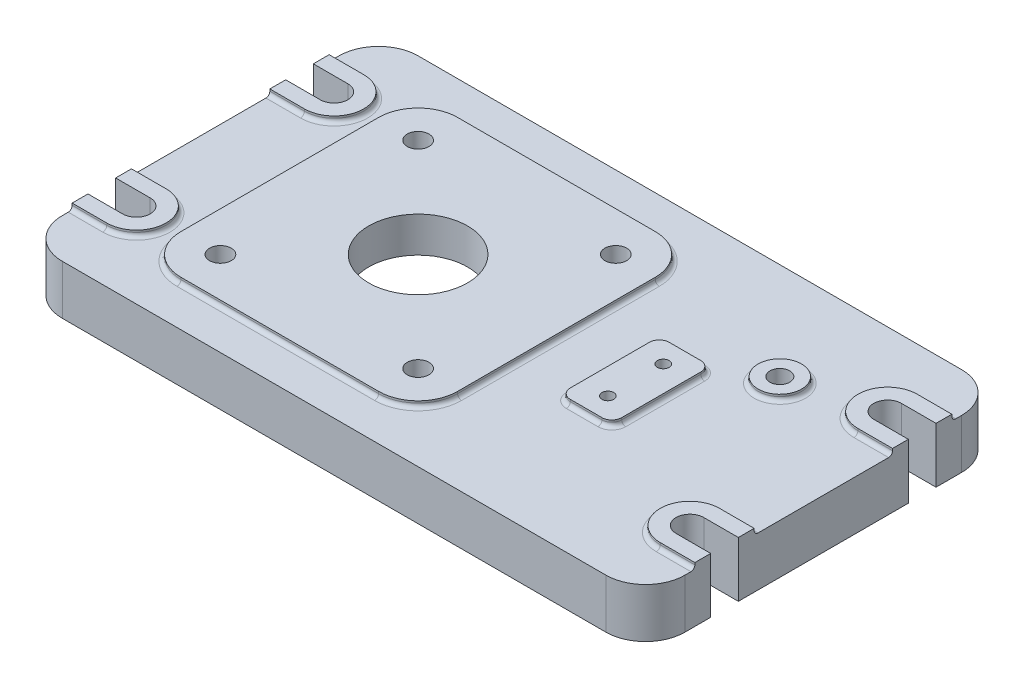
SolidWorks part; units mm, degrees
material "Gray Cast Iron"
ref_plane "Front Plane" through (0, 0, 0) normal (0, 0, 1) x (1, 0, 0)
ref_plane "Top Plane" through (0, 0, 0) normal (0, 1, 0) x (1, 0, 0)
ref_plane "Right Plane" through (0, 0, 0) normal (1, 0, 0) x (0, 0, -1)
sketch "Sketch1" plane through (0, 0, 0) normal (0, 1, 0) x (1, 0, 0)
  line L0 (-157.5, 65) -> (-140, 65)
  line L1 (-137.5, 90) -> (137.5, 90)
  line L2 (-157.5, 70) -> (-157.5, 57)
  line L3 (-137.5, -90) -> (137.5, -90)
  line L4 (157.5, 70) -> (157.5, 57)
  line L5 (-140, 35) -> (-157.5, 35)
  line L6 (-157.5, 57) -> (-140, 57)
  line L7 (-140, 43) -> (-157.5, 43)
  line L8 (-258.92, 0) -> (211.701, 0) construction
  line L9 (0, 169.4459) -> (0, -119.6728) construction
  line L10 (-140, -43) -> (-157.5, -43)
  line L11 (-157.5, -57) -> (-140, -57)
  line L12 (-140, -35) -> (-157.5, -35)
  line L13 (-157.5, -65) -> (-140, -65)
  line L14 (258.92, 0) -> (-211.701, 0) construction
  line L15 (157.5, -65) -> (140, -65)
  line L16 (140, -35) -> (157.5, -35)
  line L17 (157.5, -57) -> (140, -57)
  line L18 (140, -43) -> (157.5, -43)
  line L19 (140, 43) -> (157.5, 43)
  line L20 (157.5, 57) -> (140, 57)
  line L21 (140, 35) -> (157.5, 35)
  line L22 (157.5, 65) -> (140, 65)
  line L23 (-157.5, 43) -> (-157.5, -43)
  line L24 (-157.5, -57) -> (-157.5, -70)
  line L25 (157.5, 43) -> (157.5, -43)
  line L26 (157.5, -57) -> (157.5, -70)
  line L27 (-47.5, 101.8482) -> (-47.5, -105.2929) construction
  line L28 (-97.5, 70) -> (2.5, 70)
  line L29 (-117.5, 50) -> (-117.5, -50)
  line L30 (-97.5, -70) -> (2.5, -70)
  line L31 (22.5, 50) -> (22.5, -50)
  line L33 (54.5, 25) -> (70.5, 25)
  line L34 (49.5, 20) -> (49.5, -20)
  line L35 (54.5, -25) -> (70.5, -25)
  line L36 (75.5, 20) -> (75.5, -20)
  arc A0 (137.5, 90) -> (157.5, 70) centre (137.5, 70) cw
  arc A1 (-157.5, -70) -> (-137.5, -90) centre (-137.5, -70) ccw
  arc A2 (137.5, -90) -> (157.5, -70) centre (137.5, -70) ccw
  arc A3 (-137.5, 90) -> (-157.5, 70) centre (-137.5, 70) ccw
  arc A4 (-140, 65) -> (-140, 35) centre (-140, 50) cw
  arc A5 (-140, 57) -> (-140, 43) centre (-140, 50) cw
  arc A6 (-140, -57) -> (-140, -43) centre (-140, -50) ccw
  arc A7 (-140, -65) -> (-140, -35) centre (-140, -50) ccw
  arc A8 (140, -65) -> (140, -35) centre (140, -50) cw
  arc A9 (140, -57) -> (140, -43) centre (140, -50) cw
  arc A10 (140, 57) -> (140, 43) centre (140, 50) ccw
  arc A11 (140, 65) -> (140, 35) centre (140, 50) ccw
  arc A12 (2.5, 70) -> (22.5, 50) centre (2.5, 50) cw
  arc A13 (-117.5, -50) -> (-97.5, -70) centre (-97.5, -50) ccw
  arc A14 (2.5, -70) -> (22.5, -50) centre (2.5, -50) ccw
  arc A15 (-97.5, 70) -> (-117.5, 50) centre (-97.5, 50) ccw
  circle A16 centre (-47.5, 0) radius 25
  circle A17 centre (-97.5, 50) radius 5.5
  circle A18 centre (-97.5, -50) radius 5.5
  circle A19 centre (2.5, -50) radius 5.5
  circle A20 centre (2.5, 50) radius 5.5
  arc A21 (75.5, 20) -> (70.5, 25) centre (70.5, 20) ccw
  arc A22 (54.5, -25) -> (49.5, -20) centre (54.5, -20) cw
  arc A23 (70.5, -25) -> (75.5, -20) centre (70.5, -20) ccw
  arc A24 (54.5, 25) -> (49.5, 20) centre (54.5, 20) ccw
  circle A25 centre (62.5, 14) radius 3
  circle A26 centre (62.5, -14) radius 3
  circle A27 centre (97.5, 38) radius 11
  circle A28 centre (97.5, 38) radius 5
  point P9 (-157.5, -90)
  point P12 (157.5, -90)
  point P15 (-157.5, 90)
  point P67 (-47.5, 70)
  point P70 (22.5, 70)
  point P75 (22.5, -70)
  point P78 (-117.5, 70)
  point P89 (62.5, 25)
  point P92 (75.5, 25)
  point P95 (49.5, -25)
  point P98 (75.5, -25)
  dimension "D5" = 20
  dimension "D9" = 15
  dimension "D13" = 20
  dimension "D14" = 50
  dimension "D15" = 11
  dimension "D20" = 5
  dimension "D21" = 6
  dimension "D22" = 6
  dimension "D27" = 22
  dimension "D28" = 10
  dimension "D1" = 315
  dimension "D2" = 180
  dimension "D3" = 140
  dimension "D4" = 90
  dimension "D7" = 17.5
  dimension "D8" = 40
  dimension "D10" = 140
  dimension "D11" = 70
  dimension "D12" = 110
  dimension "D16" = 50
  dimension "D17" = 26
  dimension "D18" = 25
  dimension "D19" = 95
  dimension "D23" = 28
  dimension "D24" = 14
  dimension "D25" = 13
  dimension "D26" = 14
  dimension "D29" = 60
  dimension "D30" = 38
  dimension "D6" = 8
extrude "Boss-Extrude1" add sketch "Sketch1" along normal blind 25 contours A11 L22 L4 A0 L1 A3 L2 L0 A4 L5 L23 L12 A7 L13 L24 A1 L3 A2 L26 L15 A8 L16 L25 L21 A27 A24 L33 A21 L36 A23 L35 A22 L34 A15 L28 A12 L31 A14 L30 A13 L29 region at (24.9852, 0, 0.4524)
extrude "Boss-Extrude2" add sketch "Sketch1<3>" along normal blind 28 contours L28 A15 L29 A13 L30 A14 L31 A12 A20 A19 A18 A17 A16 | L33 A24 L34 A22 L35 A23 L36 A21 A26 A25 | A27 A28 | L22 A11 L21 L25 L19 A10 L20 L4 | L6 A5 L7 L23 L5 A4 L0 L2 | L13 A7 L12 L23 L10 A6 L11 L24 | L17 A9 L18 L25 L16 A8 L15 L26 region at (-148.75, 0, -64.5577) region at (-148.75, 0, 35.4423) region at (157.0577, 0, -61) region at (157.0577, 0, 39) region at (-47.5, 0, -68.0201) region at (62.5, 0, 0) region at (86.8111, 0, -38)
sketch "Sketch1<3>" plane through (0, 0, 0) normal (0, 1, 0) x (1, 0, 0) same geometry as "Sketch1"
sketch "Sketch2" plane through (0, 0, 0) normal (0, -1, 0) x (1, 0, 0)
  line L0 (-157.5, -43) -> (-157.5, 43) construction
  line L1 (-112.5, 70) -> (112.5, 70)
  line L2 (-117.5, 65) -> (-117.5, 30)
  line L3 (-112.5, -70) -> (112.5, -70)
  line L4 (117.5, 65) -> (117.5, 30)
  line L5 (-122.5, 25) -> (-132.5, 25)
  line L7 (-122.5, -25) -> (-132.5, -25)
  line L8 (-137.5, 20) -> (-137.5, -20)
  line L9 (122.5, 25) -> (132.5, 25)
  line L11 (122.5, -25) -> (132.5, -25)
  line L12 (137.5, 20) -> (137.5, -20)
  line L13 (157.5, -43) -> (157.5, 43) construction
  line L14 (-137.5, 90) -> (137.5, 90) construction
  line L15 (-137.5, -90) -> (137.5, -90) construction
  line L16 (-117.5, -30) -> (-117.5, -65)
  line L17 (117.5, -30) -> (117.5, -65)
  arc A0 (132.5, 25) -> (137.5, 20) centre (132.5, 20) cw
  arc A1 (132.5, -25) -> (137.5, -20) centre (132.5, -20) ccw
  arc A2 (-132.5, -25) -> (-137.5, -20) centre (-132.5, -20) cw
  arc A3 (-132.5, 25) -> (-137.5, 20) centre (-132.5, 20) ccw
  arc A4 (117.5, -30) -> (122.5, -25) centre (122.5, -30) cw
  arc A5 (122.5, 25) -> (117.5, 30) centre (122.5, 30) cw
  arc A6 (-117.5, -30) -> (-122.5, -25) centre (-122.5, -30) ccw
  arc A7 (-122.5, 25) -> (-117.5, 30) centre (-122.5, 30) ccw
  arc A8 (112.5, 70) -> (117.5, 65) centre (112.5, 65) cw
  arc A9 (-117.5, -65) -> (-112.5, -70) centre (-112.5, -65) ccw
  arc A10 (112.5, -70) -> (117.5, -65) centre (112.5, -65) ccw
  arc A11 (-112.5, 70) -> (-117.5, 65) centre (-112.5, 65) ccw
  circle A12 centre (-97.5, 50) radius 8
  circle A13 centre (2.5, 50) radius 8
  circle A14 centre (2.5, -50) radius 8
  circle A15 centre (-97.5, -50) radius 8
  circle A16 centre (62.5, -14) radius 5
  circle A17 centre (62.5, 14) radius 5
  point P20 (0, -90)
  point P24 (137.5, 25)
  point P27 (137.5, -25)
  point P30 (-137.5, -25)
  point P33 (-137.5, 25)
  point P46 (-117.5, -70)
  point P49 (117.5, -70)
  circle M32 centre (2.5, -50) radius 5.5
  circle M33 centre (2.5, 50) radius 5.5
  circle M34 centre (-97.5, 50) radius 5.5
  circle M35 centre (-97.5, -50) radius 5.5
  circle M37 centre (62.5, 14) radius 3
  circle M38 centre (62.5, -14) radius 3
  dimension "D11" = 5
  dimension "D12" = 16
  dimension "D13" = 10
  dimension "D14" = 10
  dimension "D1" = 235
  dimension "D2" = 20
  dimension "D3" = 20
  dimension "D4" = 20
  dimension "D5" = 20
  dimension "D6" = 40
  dimension "D7" = 50
  dimension "D8" = 25
  dimension "D9" = 50
  dimension "D10" = 25
extrude "Cut-Extrude1" cut sketch "Sketch2" against normal blind 10
extrude "Cut-Extrude2" cut sketch "Sketch2<2>" against normal blind 20 contours A14 M32 | M32 | A16 M38 | A17 M37 | A13 M33 | M33 | A15 M35 | M35 | A12 M34 | M34 region at (-105.2737, 0, 50) region at (-5.2737, 0, 50) region at (-5.2737, 0, -50) region at (-105.2737, 0, -50) region at (57.6414, 0, -14) region at (57.6414, 0, 14) region at (2.5, 0, -50) region at (2.5, 0, 50) region at (-97.5, 0, 50) region at (-97.5, 0, -50)
sketch "Sketch2<2>" plane through (0, 0, 0) normal (0, -1, 0) x (1, 0, 0) same geometry as "Sketch2"
fillet "Fillet1" radius 2 29 edges at (148.75, 25, -65) (125, 25, -50) (148.75, 25, 35) (125, 25, 50) (62.5, 25, 25) (50.9645, 25, 23.5355) (49.5, 25, 0) (50.9645, 25, -23.5355) (62.5, 25, -25) (74.0355, 25, -23.5355) (75.5, 25, 0) (-111.6421, 25, 64.1421) (-117.5, 25, 0) (-111.6421, 25, -64.1421) (-47.5, 25, -70) (16.6421, 25, -64.1421) (22.5, 25, 0) (16.6421, 25, 64.1421) (-148.75, 25, -65) (-148.75, 25, -35) (-148.75, 25, 65) (-148.75, 25, 35) (148.75, 25, -35) (148.75, 25, 65) (97.5, 25, -27) (74.0355, 25, 23.5355) (-47.5, 25, 70) (-125, 25, -50) (-125, 25, 50)
